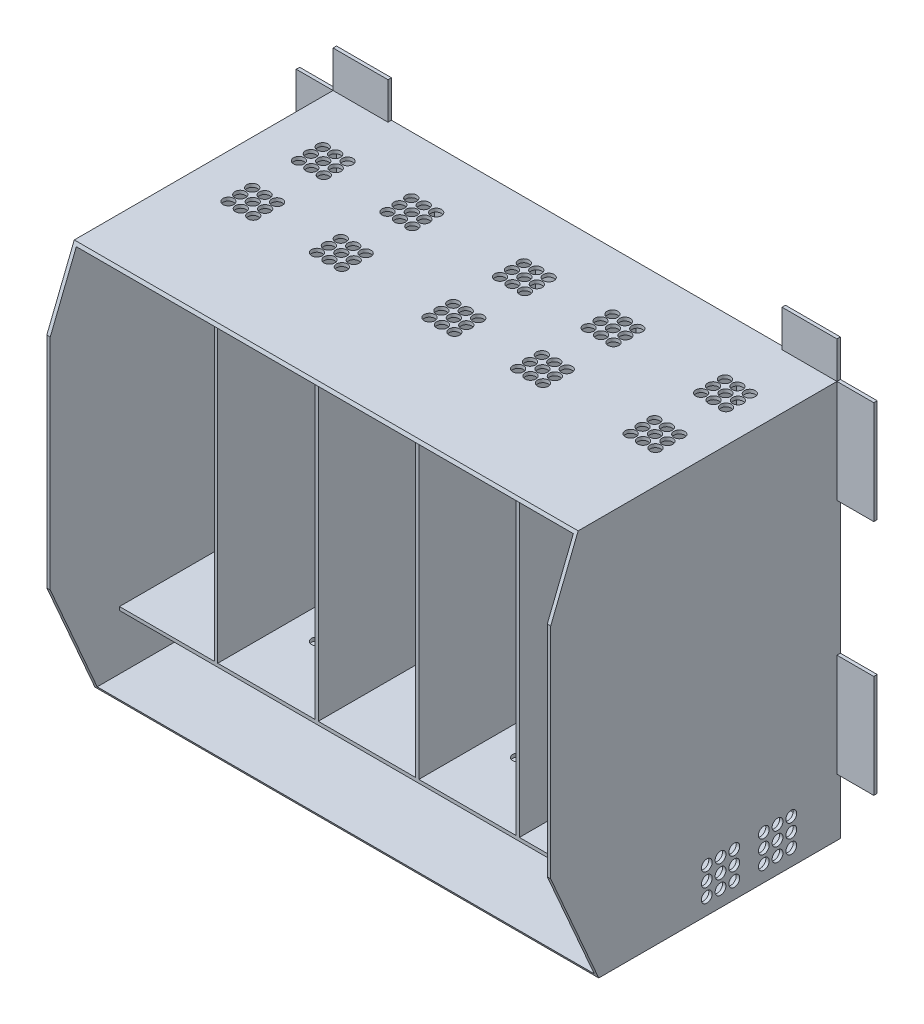
SolidWorks part; units mm, degrees
material "6061-T6 (SS)"
ref_plane "X-Y Datum" through (0, 0, 0) normal (0, 0, 1) x (1, 0, 0)
ref_plane "X-Z Datum" through (0, 0, 0) normal (0, 1, 0) x (1, 0, 0)
ref_plane "Y-Z Datum" through (0, 0, 0) normal (1, 0, 0) x (0, 0, -1)
sketch "Sketch1" plane through (0, 0, 0) normal (0, 0, 1) x (1, 0, 0)
  line L0 (-276.2265, 0) -> (276.2265, 0) construction
  line L1 (-276.2265, 154.041) -> (276.2265, 154.041)
  line L2 (-276.2265, 154.041) -> (-276.2265, -154.041)
  line L3 (-276.2265, -154.041) -> (276.2265, -154.041)
  line L4 (276.2265, 154.041) -> (276.2265, -154.041)
  line L5 (-276.2265, 154.041) -> (276.2265, -154.041) construction
  line L6 (-276.2265, -154.041) -> (276.2265, 154.041) construction
  line L7 (-275.2105, 153.025) -> (-189.6105, 153.025) construction
  line L8 (-275.2105, 153.025) -> (-275.2105, -153.025) construction
  line L9 (-275.2105, -153.025) -> (-189.6105, -153.025) construction
  line L10 (-189.6105, 153.025) -> (-189.6105, -153.025) construction
  line L11 (-275.2105, 153.025) -> (-189.6105, -153.025) construction
  line L12 (-275.2105, -153.025) -> (-189.6105, 153.025) construction
  line L13 (-188.5945, -154.041) -> (-188.5945, 154.041)
  line L14 (-279.4015, 157.216) -> (279.4015, 157.216)
  line L15 (279.4015, 157.216) -> (279.4015, -157.216)
  line L16 (-279.4015, -157.216) -> (279.4015, -157.216)
  line L17 (-279.4015, 157.216) -> (-279.4015, -157.216)
  line L18 (-185.4195, -154.041) -> (-185.4195, 154.041)
  line L19 (-188.5945, 0) -> (-185.4195, 0) construction
  line L20 (-182.2465, 153.025) -> (-182.2465, -153.025) construction
  line L21 (-182.2465, 153.025) -> (-96.6465, 153.025) construction
  line L22 (-96.6465, 153.025) -> (-96.6465, -153.025) construction
  line L23 (-182.2465, -153.025) -> (-96.6465, -153.025) construction
  line L24 (-95.6305, -154.041) -> (-95.6305, 154.041)
  line L25 (-92.4555, -154.041) -> (-92.4555, 154.041)
  line L26 (-89.2825, 153.025) -> (-89.2825, -153.025) construction
  line L27 (-89.2825, 153.025) -> (-3.6825, 153.025) construction
  line L28 (-3.6825, 153.025) -> (-3.6825, -153.025) construction
  line L29 (-89.2825, -153.025) -> (-3.6825, -153.025) construction
  line L30 (-2.6665, -154.041) -> (-2.6665, 154.041)
  line L31 (0.5085, -154.041) -> (0.5085, 154.041)
  line L32 (3.6815, 153.025) -> (3.6815, -153.025) construction
  line L33 (3.6815, 153.025) -> (89.2815, 153.025) construction
  line L34 (89.2815, 153.025) -> (89.2815, -153.025) construction
  line L35 (3.6815, -153.025) -> (89.2815, -153.025) construction
  line L36 (90.2975, -154.041) -> (90.2975, 154.041)
  line L37 (93.4725, -154.041) -> (93.4725, 154.041)
  line L38 (96.6455, 153.025) -> (96.6455, -153.025) construction
  line L39 (96.6455, 153.025) -> (182.2455, 153.025) construction
  line L40 (182.2455, 153.025) -> (182.2455, -153.025) construction
  line L41 (96.6455, -153.025) -> (182.2455, -153.025) construction
  line L42 (183.2615, -154.041) -> (183.2615, 154.041)
  line L43 (186.4365, -154.041) -> (186.4365, 154.041)
  line L44 (-182.2465, -153.025) -> (-96.6465, 153.025) construction
  line L45 (-182.2465, 153.025) -> (-96.6465, -153.025) construction
  line L46 (-89.2825, -153.025) -> (-3.6825, 153.025) construction
  line L47 (-89.2825, 153.025) -> (-3.6825, -153.025) construction
  line L48 (3.6815, -153.025) -> (89.2815, 153.025) construction
  line L49 (3.6815, 153.025) -> (89.2815, -153.025) construction
  line L50 (96.6455, -153.025) -> (182.2455, 153.025) construction
  line L51 (96.6455, 153.025) -> (182.2455, -153.025) construction
  line L52 (-276.2265, -157.216) -> (-276.2265, -208.016)
  line L53 (-279.4015, -157.216) -> (279.4015, -157.216)
  line L54 (-279.4015, -157.216) -> (-279.4015, -210.302)
  line L56 (279.4015, -157.216) -> (279.4015, -397.1906)
  line L58 (276.2265, -157.216) -> (276.2265, -392.7808)
  line L59 (186.4365, -154.041) -> (186.4365, -210.302)
  line L60 (183.2615, -157.216) -> (183.2615, -208.016)
  line L61 (186.4365, 154.041) -> (186.4365, 157.216)
  line L62 (-276.2265, -208.016) -> (276.2265, -392.7808) construction
  line L63 (-276.2265, -208.016) -> (183.2615, -208.016)
  line L64 (-279.4015, -210.302) -> (186.4365, -210.302)
  line L65 (-279.4015, -210.302) -> (279.4015, -397.1906) construction
  point P0 (0, 0)
  point P6 (-232.4105, 0)
  point P23 (-187.007, 0)
  point P24 (-139.4465, 0)
  dimension "D1" = 306.05
  dimension "D2" = 85.6
  dimension "D3" = 1.016
  dimension "D4" = 1.016
  dimension "D5" = 1.016
  dimension "D8" = 45.4035
  dimension "D10" = 89.789
  dimension "D12" = 92.964
  dimension "D13" = 89.79
  dimension "D14" = 50.8
  dimension "D16" = 2.286
  dimension "D6" = 3.175
  dimension "D7" = 3.175
  dimension "D15" = 3.175
  dimension "D9" = 5
  dimension "D11" = 5
extrude "Boss-Extrude1" add sketch "Sketch1" along normal blind 3.175 contours L3 L43 L1 L42 | L54 L64 L59 L53 L60 L63 L52 L16 | L52 L63 L60 L16 | L3 L42 L1 L37 | L3 L36 L1 L31 | L3 L31 L1 L30 | L3 L37 L1 L36 | L3 L30 L1 L25 | L1 L61 L14 L17 L16 L53 L59 L3 L2 | L3 L24 L1 L18 | L3 L13 L1 L2 | L3 L18 L1 L13 | L3 L25 L1 L24 region at (-276.7885, 0, 0) region at (-232.4105, 0, 0) region at (-187.007, 0, 0) region at (-140.525, 0, 0) region at (-94.043, 0, 0) region at (-47.561, 0, 0) region at (-1.079, 0, 0) region at (45.403, 0, 0) region at (91.885, 0, 0) region at (138.367, 0, 0) region at (184.849, 0, 0) region at (185.9676, -183.759, 0) region at (-46.4825, -182.616, 0)
sketch "Sketch2" plane through (0, 0, 3.175) normal (0, 0, 1) x (1, 0, 0)
  line L0 (-188.5945, -154.041) -> (-188.5945, 154.041) construction
  line L1 (-95.6305, -154.041) -> (-95.6305, 154.041) construction
  line L2 (-185.4195, -154.041) -> (-185.4195, 154.041) construction
  line L3 (90.2975, -154.041) -> (90.2975, 154.041) construction
  line L4 (276.2265, 154.041) -> (-276.2265, 154.041)
  line L5 (276.2265, -154.041) -> (276.2265, 154.041)
  line L6 (-276.2265, -154.041) -> (276.2265, -154.041)
  line L7 (-276.2265, 154.041) -> (-276.2265, -154.041)
  line L8 (276.2265, 154.041) -> (-276.2265, 154.041)
  line L9 (276.2265, -154.041) -> (276.2265, 154.041)
  line L10 (-276.2265, -154.041) -> (276.2265, -154.041)
  line L11 (-276.2265, 154.041) -> (-276.2265, -154.041)
  line L12 (-279.4015, -157.216) -> (279.4015, -157.216)
  line L13 (-279.4015, -157.216) -> (279.4015, -157.216) construction
  line L14 (279.4015, 157.216) -> (279.4015, -157.216) construction
  line L15 (-279.4015, 157.216) -> (279.4015, 157.216) construction
  line L16 (-279.4015, -157.216) -> (279.4015, -157.216)
  line L20 (0.5085, -154.041) -> (0.5085, 154.041) construction
  line L21 (-2.6665, -154.041) -> (-2.6665, 154.041) construction
  line L22 (-92.4555, -154.041) -> (-92.4555, 154.041) construction
  line L23 (186.4365, -154.041) -> (186.4365, 154.041) construction
  line L24 (183.2615, -154.041) -> (183.2615, 154.041) construction
  line L25 (93.4725, -154.041) -> (93.4725, 154.041) construction
  line L26 (-188.5945, -154.041) -> (-188.5945, 154.041)
  line L27 (-95.6305, -154.041) -> (-95.6305, 154.041)
  line L28 (-185.4195, -154.041) -> (-185.4195, 154.041)
  line L29 (90.2975, -154.041) -> (90.2975, 154.041)
  line L30 (0.5085, -154.041) -> (0.5085, 154.041)
  line L31 (-2.6665, -154.041) -> (-2.6665, 154.041)
  line L32 (-92.4555, -154.041) -> (-92.4555, 154.041)
  line L33 (186.4365, -154.041) -> (186.4365, 154.041)
  line L34 (183.2615, -154.041) -> (183.2615, 154.041)
  line L35 (93.4725, -154.041) -> (93.4725, 154.041)
  line L36 (-279.4015, 157.216) -> (-279.4015, -157.216) construction
  line L37 (-279.4015, -157.216) -> (279.4015, -157.216) construction
  line L38 (-279.4015, -157.216) -> (-279.4015, -210.302) construction
  line L41 (-276.2265, -157.216) -> (-276.2265, -208.016) construction
  line L44 (-276.2265, 154.041) -> (276.2265, 154.041) construction
  line L45 (276.2265, 154.041) -> (276.2265, -154.041) construction
  line L46 (-276.2265, -154.041) -> (276.2265, -154.041) construction
  line L47 (-276.2265, 154.041) -> (-276.2265, -154.041) construction
  line L48 (-188.5945, -154.041) -> (-188.5945, 154.041)
  line L49 (-95.6305, -154.041) -> (-95.6305, 154.041)
  line L50 (-185.4195, -154.041) -> (-185.4195, 154.041)
  line L51 (-279.4015, -157.216) -> (279.4015, -157.216)
  line L52 (279.4015, 157.216) -> (279.4015, -157.216)
  line L53 (-279.4015, 157.216) -> (279.4015, 157.216)
  line L54 (-279.4015, 157.216) -> (-279.4015, -157.216)
  line L55 (-279.4015, -157.216) -> (279.4015, -157.216)
  line L56 (-279.4015, -157.216) -> (-279.4015, -210.302)
  line L59 (90.2975, -154.041) -> (90.2975, 154.041)
  line L60 (0.5085, -154.041) -> (0.5085, 154.041)
  line L61 (-2.6665, -154.041) -> (-2.6665, 154.041)
  line L62 (-92.4555, -154.041) -> (-92.4555, 154.041)
  line L63 (186.4365, -154.041) -> (186.4365, 154.041)
  line L64 (183.2615, -154.041) -> (183.2615, 154.041)
  line L65 (93.4725, -154.041) -> (93.4725, 154.041)
  line L66 (-276.2265, -157.216) -> (-276.2265, -208.016)
  line L67 (-279.4015, -210.302) -> (186.4365, -210.302) construction
  line L69 (-276.2265, 154.041) -> (276.2265, 154.041)
  line L70 (276.2265, 154.041) -> (276.2265, -154.041)
  line L71 (-276.2265, -154.041) -> (276.2265, -154.041)
  line L72 (-276.2265, 154.041) -> (-276.2265, -154.041)
  line L73 (183.2615, -157.216) -> (183.2615, -208.016) construction
  line L74 (186.4365, 154.041) -> (186.4365, 157.216) construction
  line L75 (186.4365, -154.041) -> (186.4365, -210.302) construction
  line L76 (-188.5945, -154.041) -> (-188.5945, 154.041)
  line L77 (-95.6305, -154.041) -> (-95.6305, 154.041)
  line L78 (-185.4195, -154.041) -> (-185.4195, 154.041)
  line L79 (-279.4015, -157.216) -> (279.4015, -157.216)
  line L80 (279.4015, 157.216) -> (279.4015, -157.216)
  line L81 (-279.4015, 157.216) -> (279.4015, 157.216)
  line L82 (-279.4015, 157.216) -> (-279.4015, -157.216)
  line L83 (-279.4015, -157.216) -> (279.4015, -157.216)
  line L84 (-279.4015, -157.216) -> (-279.4015, -210.302)
  line L85 (-276.2265, -208.016) -> (183.2615, -208.016) construction
  line L87 (90.2975, -154.041) -> (90.2975, 154.041)
  line L88 (0.5085, -154.041) -> (0.5085, 154.041)
  line L89 (-2.6665, -154.041) -> (-2.6665, 154.041)
  line L90 (-92.4555, -154.041) -> (-92.4555, 154.041)
  line L91 (183.2615, -154.041) -> (183.2615, 154.041)
  line L92 (93.4725, -154.041) -> (93.4725, 154.041)
  line L93 (183.2615, -157.216) -> (183.2615, -208.016)
  line L94 (-276.2265, -157.216) -> (-276.2265, -208.016)
  line L97 (186.4365, 154.041) -> (186.4365, 157.216)
  line L98 (186.4365, -154.041) -> (186.4365, 154.041)
  line L99 (186.4365, -154.041) -> (186.4365, -210.302)
  line L100 (-276.2265, 154.041) -> (276.2265, 154.041)
  line L101 (276.2265, 154.041) -> (276.2265, -154.041)
  line L102 (-276.2265, -154.041) -> (276.2265, -154.041)
  line L103 (-276.2265, 154.041) -> (-276.2265, -154.041)
  line L104 (-188.5945, -154.041) -> (-188.5945, 154.041)
  line L106 (-95.6305, -154.041) -> (-95.6305, 154.041)
  line L107 (-185.4195, -154.041) -> (-185.4195, 154.041)
  line L108 (-279.4015, -157.216) -> (279.4015, -157.216)
  line L109 (279.4015, 157.216) -> (279.4015, -157.216)
  line L110 (-279.4015, 157.216) -> (279.4015, 157.216)
  line L111 (-279.4015, 157.216) -> (-279.4015, -157.216)
  line L112 (-279.4015, -157.216) -> (279.4015, -157.216)
  line L113 (186.4365, 154.041) -> (186.4365, 157.216)
  line L114 (186.4365, -154.041) -> (186.4365, 154.041)
  line L115 (186.4365, -154.041) -> (186.4365, -210.302)
  line L116 (-279.4015, -210.302) -> (186.4365, -210.302)
  line L117 (-279.4015, -157.216) -> (-279.4015, -210.302)
  line L118 (90.2975, -154.041) -> (90.2975, 154.041)
  line L119 (0.5085, -154.041) -> (0.5085, 154.041)
  line L120 (-2.6665, -154.041) -> (-2.6665, 154.041)
  line L121 (-92.4555, -154.041) -> (-92.4555, 154.041)
  line L122 (183.2615, -154.041) -> (183.2615, 154.041)
  line L123 (93.4725, -154.041) -> (93.4725, 154.041)
  line L124 (183.2615, -157.216) -> (183.2615, -208.016)
  line L125 (-276.2265, -208.016) -> (183.2615, -208.016)
  line L126 (-276.2265, -157.216) -> (-276.2265, -208.016)
  line L128 (-276.2265, 154.041) -> (276.2265, 154.041)
  line L129 (276.2265, 154.041) -> (276.2265, -154.041)
  line L130 (-276.2265, -154.041) -> (276.2265, -154.041)
  line L131 (-276.2265, 154.041) -> (-276.2265, -154.041)
  line M9 (186.4365, 157.216) -> (-279.4015, 157.216)
  line M10 (-279.4015, 157.216) -> (-279.4015, -210.302)
  line M86 (186.4365, -210.302) -> (186.4365, 157.216)
  line M120 (-279.4015, -210.302) -> (186.4365, -210.302)
  dimension "D1" = 0
  dimension "D2" = 0
extrude "Boss-Extrude2" add sketch "Sketch2" along normal blind 200.6 contours L125 L66 L16 L83 L93 M10 M120 M86 | L16 L55 L83 L10 L11 L8 M10 M86 M9 | L34 L10 L8 M86 | L10 L35 L8 L29 | L10 L28 L8 L26 | L10 L32 L8 L27 | L31 L10 L30 L8 region at (184.849, 0, 3.175) region at (184.849, 154.603, 3.175) region at (91.885, 0, 3.175) region at (185.9676, -183.759, 3.175) region at (-1.079, 0, 3.175) region at (-94.043, 0, 3.175) region at (-187.007, 0, 3.175)
sketch "Sketch11" plane through (0, 0, 203.775) normal (0, 0, 1) x (1, 0, 0)
  line L0 (-188.5945, -154.041) -> (-188.5945, 154.041) construction
  line L2 (-95.6305, -154.041) -> (-95.6305, 154.041) construction
  line L3 (-185.4195, -154.041) -> (-185.4195, 154.041) construction
  line L4 (186.4365, -210.302) -> (186.4365, 157.216)
  line L5 (186.4365, 157.216) -> (-279.4015, 157.216)
  line L6 (-279.4015, 157.216) -> (-279.4015, -210.302)
  line L7 (-279.4015, -210.302) -> (186.4365, -210.302)
  line L8 (186.4365, -210.302) -> (186.4365, 157.216)
  line L9 (186.4365, 157.216) -> (-279.4015, 157.216)
  line L10 (-279.4015, 157.216) -> (-279.4015, -210.302)
  line L11 (-279.4015, -210.302) -> (186.4365, -210.302)
  line L12 (-279.4015, -157.216) -> (279.4015, -157.216) construction
  line L14 (-279.4015, 157.216) -> (279.4015, 157.216) construction
  line L15 (-279.4015, 157.216) -> (-279.4015, -157.216) construction
  line L16 (-279.4015, -157.216) -> (279.4015, -157.216) construction
  line L17 (186.4365, 154.041) -> (186.4365, 157.216) construction
  line L18 (186.4365, -154.041) -> (186.4365, 154.041) construction
  line L19 (186.4365, -154.041) -> (186.4365, -210.302) construction
  line L20 (-279.4015, -210.302) -> (186.4365, -210.302) construction
  line L21 (-279.4015, -157.216) -> (-279.4015, -210.302) construction
  line L22 (90.2975, -154.041) -> (90.2975, 154.041) construction
  line L23 (0.5085, -154.041) -> (0.5085, 154.041) construction
  line L24 (-2.6665, -154.041) -> (-2.6665, 154.041) construction
  line L25 (-92.4555, -154.041) -> (-92.4555, 154.041) construction
  line L26 (183.2615, -154.041) -> (183.2615, 154.041) construction
  line L27 (93.4725, -154.041) -> (93.4725, 154.041) construction
  line L28 (183.2615, -157.216) -> (183.2615, -208.016) construction
  line L29 (-276.2265, -208.016) -> (183.2615, -208.016) construction
  line L30 (-276.2265, -157.216) -> (-276.2265, -208.016) construction
  line L32 (-276.2265, 154.041) -> (276.2265, 154.041) construction
  line L34 (-276.2265, -154.041) -> (276.2265, -154.041) construction
  line L35 (-276.2265, 154.041) -> (-276.2265, -154.041) construction
  line L36 (-188.5945, -154.041) -> (-188.5945, 154.041)
  line L37 (183.2615, -157.216) -> (183.2615, -154.041)
  line L38 (-95.6305, -154.041) -> (-95.6305, 154.041)
  line L39 (-185.4195, -154.041) -> (-185.4195, 154.041)
  line L40 (-279.4015, -157.216) -> (186.4365, -157.216)
  line L42 (-279.4015, 157.216) -> (186.4365, 157.216)
  line L43 (-279.4015, 157.216) -> (-279.4015, -157.216)
  line L44 (-279.4015, -157.216) -> (186.4365, -157.216)
  line L45 (186.4365, 154.041) -> (186.4365, 157.216)
  line L46 (186.4365, -154.041) -> (186.4365, 154.041)
  line L47 (186.4365, -154.041) -> (186.4365, -210.302)
  line L48 (-279.4015, -210.302) -> (186.4365, -210.302)
  line L49 (-279.4015, -157.216) -> (-279.4015, -210.302)
  line L50 (90.2975, -154.041) -> (90.2975, 154.041)
  line L51 (0.5085, -154.041) -> (0.5085, 154.041)
  line L52 (-2.6665, -154.041) -> (-2.6665, 154.041)
  line L53 (-92.4555, -154.041) -> (-92.4555, 154.041)
  line L54 (183.2615, -154.041) -> (183.2615, 154.041)
  line L55 (93.4725, -154.041) -> (93.4725, 154.041)
  line L56 (183.2615, -157.216) -> (183.2615, -208.016)
  line L57 (-276.2265, -208.016) -> (183.2615, -208.016)
  line L58 (-276.2265, -157.216) -> (-276.2265, -208.016)
  line L59 (-276.2265, -157.216) -> (-276.2265, -154.041)
  line L60 (-276.2265, 154.041) -> (186.4365, 154.041)
  line L62 (-276.2265, -154.041) -> (186.4365, -154.041)
  line L63 (-276.2265, 154.041) -> (-276.2265, -154.041)
  line M7 (-185.4195, 154.041) -> (-95.6305, 154.041)
  line M11 (-92.4555, 154.041) -> (-2.6665, 154.041)
  line M15 (0.5085, 154.041) -> (90.2975, 154.041)
  line M19 (93.4725, 154.041) -> (183.2615, 154.041)
  line M20 (183.2615, 154.041) -> (183.2615, -154.041)
  line M21 (186.4365, -210.302) -> (186.4365, 157.216)
  line M22 (186.4365, 157.216) -> (-279.4015, 157.216)
  line M23 (-279.4015, 157.216) -> (-279.4015, -210.302)
  line M24 (-279.4015, -210.302) -> (186.4365, -210.302)
  line M25 (-276.2265, -208.016) -> (-276.2265, -157.216)
  line M27 (183.2615, -157.216) -> (183.2615, -208.016)
  line M28 (183.2615, -208.016) -> (-276.2265, -208.016)
  line M31 (-276.2265, -154.041) -> (-276.2265, 154.041)
  line M32 (-276.2265, 154.041) -> (-188.5945, 154.041)
  dimension "D1" = 0
extrude "Boss-Extrude8" add sketch "Sketch11" along normal blind 64.05 contours L40 L10 M24 M21 M27 M28 M25 | L62 L60 M20 M21 | L62 L37 L40 L8 | L60 L40 L59 M32 M7 M11 M15 M19 M21 M22 M23 M31 region at (-46.4825, -209.8331, 203.775) region at (184.849, -155.6285, 203.775) region at (184.849, 0, 203.775) region at (-278.8395, 0, 203.775)
sketch "Sketch10" plane through (0, 0, 0) normal (0, 0, 1) x (1, 0, 0)
  line L1 (186.4365, 157.216) -> (220.4725, 157.216)
  line L2 (186.4365, 157.216) -> (186.4365, 61.966)
  line L3 (186.4365, 61.966) -> (220.4725, 61.966)
  line L4 (186.4365, -210.302) -> (186.4365, 157.216)
  line L5 (-279.4015, -210.302) -> (186.4365, -210.302)
  line L6 (-279.4015, 157.216) -> (-279.4015, -210.302)
  line L7 (186.4365, 157.216) -> (-279.4015, 157.216)
  line L8 (186.4365, -210.302) -> (186.4365, 157.216)
  line L10 (-279.4015, 157.216) -> (-279.4015, -210.302)
  line L11 (186.4365, 157.216) -> (-279.4015, 157.216)
  line L12 (220.4725, 157.216) -> (220.4725, 61.966)
  line L13 (-276.2265, -157.216) -> (183.2615, -157.216) construction
  line L14 (-276.2265, -157.216) -> (183.2615, -157.216)
  line L15 (186.4365, -157.216) -> (220.4725, -157.216)
  line L16 (186.4365, -157.216) -> (186.4365, -61.966)
  line L17 (186.4365, -61.966) -> (220.4725, -61.966)
  line L18 (220.4725, -157.216) -> (220.4725, -61.966)
  line L19 (186.4365, 157.216) -> (135.6365, 157.216)
  line L20 (186.4365, 157.216) -> (186.4365, 191.252)
  line L21 (186.4365, 191.252) -> (135.6365, 191.252)
  line L22 (135.6365, 157.216) -> (135.6365, 191.252)
  line L26 (-279.4015, -210.302) -> (186.4365, -210.302)
  dimension "D2" = 34.036
  dimension "D3" = 95.25
  dimension "D4" = 50.8
  dimension "D1" = 0
extrude "Boss-Extrude7" add sketch "Sketch10" along normal blind 3.175 contours L12 L1 L2 L3 | L15 L18 L17 L8 | L22 L11 L20 L21 region at (203.4545, 109.591, 0) region at (161.0365, 174.234, 0) region at (203.4545, -109.591, 0)
ref_plane "Plane1" through (-46.4825, 0, 0) normal (-1, 0, 0) x (0, 0, 1)
mirror "Mirror1" about plane through (-46.4825, 0, 0) normal (-1, 0, 0) of "Boss-Extrude7"
sketch "Sketch12" plane through (186.4365, 0, 0) normal (1, 0, 0) x (0, 0, -1)
  line L0 (-223.375, -210.302) -> (-267.825, -108.702)
  line L1 (-267.825, 93.716) -> (-242.425, 157.216)
  line L10 (0, -210.302) -> (0, -157.216)
  line L11 (0, -157.216) -> (-3.175, -157.216)
  line L12 (-3.175, -157.216) -> (-3.175, -61.966)
  line L13 (-3.175, -61.966) -> (0, -61.966)
  line L14 (0, -61.966) -> (0, 61.966)
  line L15 (0, 61.966) -> (-3.175, 61.966)
  line L16 (-3.175, 61.966) -> (-3.175, 157.216)
  line L17 (-3.175, 157.216) -> (-267.825, 157.216)
  line L18 (-267.825, 157.216) -> (-267.825, -210.302)
  line L19 (-267.825, -210.302) -> (0, -210.302)
  line L20 (0, -210.302) -> (0, -157.216)
  line L21 (0, -157.216) -> (-3.175, -157.216)
  line L22 (-3.175, -157.216) -> (-3.175, -61.966)
  line L23 (-3.175, -61.966) -> (0, -61.966)
  line L24 (0, -61.966) -> (0, 61.966)
  line L25 (0, 61.966) -> (-3.175, 61.966)
  line L26 (-3.175, 61.966) -> (-3.175, 157.216)
  line L27 (-3.175, 157.216) -> (-267.825, 157.216)
  line L28 (-267.825, 157.216) -> (-267.825, -210.302)
  line L29 (-267.825, -210.302) -> (0, -210.302)
  line M18 (-3.175, 157.216) -> (-267.825, 157.216)
  line M19 (-267.825, 157.216) -> (-267.825, -210.302)
  line M20 (-267.825, -210.302) -> (0, -210.302)
  dimension "D2" = 44.45
  dimension "D3" = 101.6
  dimension "D4" = 25.4
  dimension "D5" = 63.5
  dimension "D1" = 0
extrude "Cut-Extrude1" cut sketch "Sketch12" against normal through all contours L0 M20 M19 | L1 M19 M18 region at (186.4365, -176.4353, 253.0083) region at (186.4365, 136.0493, 259.3583)
sketch "Sketch13" plane through (0, 157.216, 0) normal (0, 1, 0) x (1, 0, 0)
  circle A0 centre (-238.9105, -118.4317) radius 5 construction
  circle A1 centre (-238.9105, -129.4317) radius 5 construction
  circle A2 centre (-238.9105, -140.4317) radius 5 construction
  circle A3 centre (-227.4105, -140.4317) radius 5 construction
  circle A4 centre (-227.4105, -129.4317) radius 5 construction
  circle A5 centre (-227.4105, -118.4317) radius 5 construction
  circle A6 centre (-215.9105, -118.4317) radius 5 construction
  circle A7 centre (-215.9105, -129.4317) radius 5 construction
  circle A8 centre (-215.9105, -140.4317) radius 5 construction
  circle A9 centre (-238.9105, -118.4317) radius 5
  circle A10 centre (-238.9105, -129.4317) radius 5
  circle A11 centre (-238.9105, -140.4317) radius 5
  circle A12 centre (-227.4105, -140.4317) radius 5
  circle A13 centre (-227.4105, -129.4317) radius 5
  circle A14 centre (-227.4105, -118.4317) radius 5
  circle A15 centre (-215.9105, -118.4317) radius 5
  circle A16 centre (-215.9105, -129.4317) radius 5
  circle A17 centre (-215.9105, -140.4317) radius 5
  circle A18 centre (-215.9105, -53.2317) radius 5 construction
  circle A19 centre (-215.9105, -53.2317) radius 5
  circle A20 centre (-215.9105, -75.2317) radius 5 construction
  circle A21 centre (-227.4105, -75.2317) radius 5 construction
  circle A22 centre (-238.9105, -75.2317) radius 5 construction
  circle A23 centre (-238.9105, -64.2317) radius 5 construction
  circle A24 centre (-227.4105, -64.2317) radius 5 construction
  circle A25 centre (-215.9105, -64.2317) radius 5 construction
  circle A26 centre (-227.4105, -53.2317) radius 5 construction
  circle A27 centre (-238.9105, -53.2317) radius 5 construction
  circle A28 centre (-215.9105, -75.2317) radius 5
  circle A29 centre (-227.4105, -75.2317) radius 5
  circle A30 centre (-238.9105, -75.2317) radius 5
  circle A31 centre (-238.9105, -64.2317) radius 5
  circle A32 centre (-227.4105, -64.2317) radius 5
  circle A33 centre (-215.9105, -64.2317) radius 5
  circle A34 centre (-215.9105, -53.2317) radius 5
  circle A35 centre (-227.4105, -53.2317) radius 5
  circle A36 centre (-238.9105, -53.2317) radius 5
  circle A37 centre (-145.525, -140.4317) radius 5 construction
  circle A38 centre (-145.525, -129.4317) radius 5 construction
  circle A39 centre (-145.525, -118.4317) radius 5 construction
  circle A40 centre (-157.025, -118.4317) radius 5 construction
  circle A41 centre (-157.025, -129.4317) radius 5 construction
  circle A42 centre (-157.025, -140.4317) radius 5 construction
  circle A43 centre (-145.525, -140.4317) radius 5
  circle A44 centre (-145.525, -129.4317) radius 5
  circle A45 centre (-145.525, -118.4317) radius 5
  circle A46 centre (-157.025, -118.4317) radius 5
  circle A47 centre (-157.025, -129.4317) radius 5
  circle A48 centre (-157.025, -140.4317) radius 5
  circle A49 centre (-134.025, -118.4317) radius 5 construction
  circle A50 centre (-134.025, -140.4317) radius 5 construction
  circle A51 centre (-134.025, -129.4317) radius 5 construction
  circle A52 centre (-134.025, -118.4317) radius 5
  circle A53 centre (-134.025, -140.4317) radius 5
  circle A54 centre (-134.025, -129.4317) radius 5
  circle A55 centre (-157.025, -75.2317) radius 5 construction
  circle A56 centre (-145.525, -75.2317) radius 5 construction
  circle A57 centre (-134.025, -75.2317) radius 5 construction
  circle A58 centre (-157.025, -75.2317) radius 5
  circle A59 centre (-145.525, -75.2317) radius 5
  circle A60 centre (-134.025, -75.2317) radius 5
  circle A61 centre (-134.025, -53.2317) radius 5 construction
  circle A62 centre (-145.525, -53.2317) radius 5 construction
  circle A63 centre (-157.025, -53.2317) radius 5 construction
  circle A64 centre (-157.025, -64.2317) radius 5 construction
  circle A65 centre (-134.025, -64.2317) radius 5 construction
  circle A66 centre (-145.525, -64.2317) radius 5 construction
  circle A67 centre (-134.025, -53.2317) radius 5
  circle A68 centre (-145.525, -53.2317) radius 5
  circle A69 centre (-157.025, -53.2317) radius 5
  circle A70 centre (-157.025, -64.2317) radius 5
  circle A71 centre (-134.025, -64.2317) radius 5
  circle A72 centre (-145.525, -64.2317) radius 5
  point P109 (0, 0)
  point P110 (0, 0)
extrude "Cut-Extrude2" cut sketch "Sketch13" against normal up to surface (3.175 mm away) contours A35 | A36 | A31 | A32 | A33 | A30 | A29 | A28 | A10 | A13 | A11 | A12 | A17 | A16 | A15 | A19 | A9 | A14 region at (-238.9105, 157.216, 129.4317) region at (-238.9105, 157.216, 140.4317) region at (-227.4105, 157.216, 140.4317) region at (-227.4105, 157.216, 129.4317) region at (-215.9105, 157.216, 118.4317) region at (-215.9105, 157.216, 129.4317) region at (-215.9105, 157.216, 140.4317) region at (-215.9105, 157.216, 75.2317) region at (-227.4105, 157.216, 75.2317) region at (-238.9105, 157.216, 75.2317) region at (-238.9105, 157.216, 64.2317) region at (-227.4105, 157.216, 64.2317) region at (-215.9105, 157.216, 64.2317) region at (-227.4105, 157.216, 53.2317) region at (-238.9105, 157.216, 53.2317) up to face at (-47.3453, 154.041, 107.467)
pattern_linear "LPattern1" count 3 spacing 185.92 along (1, 0, 0) of "Cut-Extrude2"
sketch "Sketch14" plane through (0, 157.216, 0) normal (0, 1, 0) x (1, 0, 0)
  circle A1 centre (-215.9105, -53.2317) radius 5
  circle A2 centre (-215.9105, -53.2317) radius 5
  circle A3 centre (-215.9105, -140.4317) radius 5
  circle A4 centre (-215.9105, -140.4317) radius 5
  circle A5 centre (-215.9105, -129.4317) radius 5
  circle A6 centre (-215.9105, -129.4317) radius 5
  circle A7 centre (-215.9105, -118.4317) radius 5
  circle A8 centre (-215.9105, -118.4317) radius 5
  circle A9 centre (-227.4105, -118.4317) radius 5
  circle A10 centre (-227.4105, -118.4317) radius 5
  circle A11 centre (-227.4105, -129.4317) radius 5
  circle A12 centre (-227.4105, -129.4317) radius 5
  circle A13 centre (-227.4105, -140.4317) radius 5
  circle A14 centre (-227.4105, -140.4317) radius 5
  circle A15 centre (-238.9105, -140.4317) radius 5
  circle A16 centre (-238.9105, -140.4317) radius 5
  circle A17 centre (-238.9105, -129.4317) radius 5
  circle A18 centre (-238.9105, -129.4317) radius 5
  circle A19 centre (-238.9105, -118.4317) radius 5
  circle A20 centre (-238.9105, -118.4317) radius 5
  circle A21 centre (-227.4105, -75.2317) radius 5
  circle A22 centre (-227.4105, -75.2317) radius 5
  circle A23 centre (-215.9105, -75.2317) radius 5
  circle A24 centre (-215.9105, -75.2317) radius 5
  circle A25 centre (-238.9105, -53.2317) radius 5
  circle A26 centre (-238.9105, -53.2317) radius 5
  circle A27 centre (-227.4105, -53.2317) radius 5
  circle A28 centre (-227.4105, -53.2317) radius 5
  circle A29 centre (-215.9105, -53.2317) radius 5
  circle A30 centre (-215.9105, -53.2317) radius 5
  circle A31 centre (-215.9105, -64.2317) radius 5
  circle A32 centre (-215.9105, -64.2317) radius 5
  circle A33 centre (-227.4105, -64.2317) radius 5
  circle A34 centre (-227.4105, -64.2317) radius 5
  circle A35 centre (-238.9105, -64.2317) radius 5
  circle A36 centre (-238.9105, -64.2317) radius 5
  circle A37 centre (-238.9105, -75.2317) radius 5
  circle A38 centre (-238.9105, -75.2317) radius 5
  circle A39 centre (-134.025, -118.4317) radius 5
  circle A40 centre (-134.025, -118.4317) radius 5
  circle A41 centre (-157.025, -140.4317) radius 5
  circle A42 centre (-157.025, -140.4317) radius 5
  circle A43 centre (-157.025, -129.4317) radius 5
  circle A44 centre (-157.025, -129.4317) radius 5
  circle A45 centre (-157.025, -118.4317) radius 5
  circle A46 centre (-157.025, -118.4317) radius 5
  circle A47 centre (-145.525, -118.4317) radius 5
  circle A48 centre (-145.525, -118.4317) radius 5
  circle A49 centre (-145.525, -129.4317) radius 5
  circle A50 centre (-145.525, -129.4317) radius 5
  circle A51 centre (-145.525, -140.4317) radius 5
  circle A52 centre (-145.525, -140.4317) radius 5
  circle A53 centre (-134.025, -75.2317) radius 5
  circle A54 centre (-134.025, -75.2317) radius 5
  circle A55 centre (-145.525, -75.2317) radius 5
  circle A56 centre (-145.525, -75.2317) radius 5
  circle A57 centre (-157.025, -75.2317) radius 5
  circle A58 centre (-157.025, -75.2317) radius 5
  circle A59 centre (-134.025, -129.4317) radius 5
  circle A60 centre (-134.025, -129.4317) radius 5
  circle A61 centre (-134.025, -140.4317) radius 5
  circle A62 centre (-134.025, -140.4317) radius 5
  circle A63 centre (-145.525, -64.2317) radius 5
  circle A64 centre (-145.525, -64.2317) radius 5
  circle A65 centre (-134.025, -64.2317) radius 5
  circle A66 centre (-134.025, -64.2317) radius 5
  circle A67 centre (-157.025, -64.2317) radius 5
  circle A68 centre (-157.025, -64.2317) radius 5
  circle A69 centre (-157.025, -53.2317) radius 5
  circle A70 centre (-157.025, -53.2317) radius 5
  circle A71 centre (-145.525, -53.2317) radius 5
  circle A72 centre (-145.525, -53.2317) radius 5
  circle A73 centre (-134.025, -53.2317) radius 5
  circle A74 centre (-134.025, -53.2317) radius 5
  dimension "D1" = 0
  dimension "D2" = 0
  dimension "D3" = 0
  dimension "D4" = 0
  dimension "D5" = 0
  dimension "D6" = 0
  dimension "D7" = 0
  dimension "D8" = 0
  dimension "D9" = 0
  dimension "D10" = 0
  dimension "D11" = 0
  dimension "D12" = 0
  dimension "D13" = 0
  dimension "D14" = 0
  dimension "D15" = 0
  dimension "D16" = 0
  dimension "D17" = 0
  dimension "D18" = 0
  dimension "D19" = 0
  dimension "D20" = 0
  dimension "D21" = 0
  dimension "D22" = 0
  dimension "D23" = 0
  dimension "D24" = 0
  dimension "D25" = 0
  dimension "D26" = 0
  dimension "D27" = 0
  dimension "D28" = 0
  dimension "D29" = 0
  dimension "D30" = 0
  dimension "D31" = 0
  dimension "D32" = 0
  dimension "D33" = 0
  dimension "D34" = 0
  dimension "D35" = 0
  dimension "D36" = 0
  dimension "D37" = 0
extrude "Cut-Extrude3" cut sketch "Sketch14" against normal up to surface (3.175 mm away) contours A42 | A52 | A62 | A60 | A50 | A44 | A46 | A48 | A40 | A56 | A54 | A66 | A64 | A68 | A70 | A72 | A74 | A58 region at (-134.025, 157.216, 118.4317) region at (-157.025, 157.216, 140.4317) region at (-157.025, 157.216, 129.4317) region at (-157.025, 157.216, 118.4317) region at (-145.525, 157.216, 118.4317) region at (-145.525, 157.216, 129.4317) region at (-145.525, 157.216, 140.4317) region at (-134.025, 157.216, 75.2317) region at (-145.525, 157.216, 75.2317) region at (-134.025, 157.216, 129.4317) region at (-134.025, 157.216, 140.4317) region at (-145.525, 157.216, 64.2317) region at (-134.025, 157.216, 64.2317) region at (-157.025, 157.216, 64.2317) region at (-157.025, 157.216, 53.2317) region at (-145.525, 157.216, 53.2317) region at (-134.025, 157.216, 53.2317) up to face at (-36.4905, 154.041, 140.4317)
pattern_linear "LPattern2" count 2 spacing 185.92 along (1, 0, 0) of "Cut-Extrude3"
sketch "Sketch16" plane through (0, -157.216, 0) normal (0, -1, 0) x (1, 0, 0)
  circle A0 centre (-215.9105, 140.4317) radius 5 construction
  circle A1 centre (-227.4105, 140.4317) radius 5 construction
  circle A2 centre (-238.9105, 140.4317) radius 5 construction
  circle A3 centre (-215.9105, 129.4317) radius 5 construction
  circle A4 centre (-238.9105, 129.4317) radius 5 construction
  circle A5 centre (-227.4105, 129.4317) radius 5 construction
  circle A6 centre (-215.9105, 118.4317) radius 5 construction
  circle A7 centre (-227.4105, 118.4317) radius 5 construction
  circle A8 centre (-238.9105, 118.4317) radius 5 construction
  circle A9 centre (-215.9105, 107.4317) radius 5 construction
  circle A10 centre (-227.4105, 107.4317) radius 5 construction
  circle A11 centre (-238.9105, 107.4317) radius 5 construction
  circle A12 centre (-215.9105, 96.4317) radius 5 construction
  circle A13 centre (-227.4105, 96.4317) radius 5 construction
  circle A14 centre (-238.9105, 96.4317) radius 5 construction
  circle A15 centre (-215.9105, 85.4317) radius 5 construction
  circle A16 centre (-227.4105, 74.4317) radius 5 construction
  circle A17 centre (-227.4105, 85.4317) radius 5 construction
  circle A18 centre (-238.9105, 85.4317) radius 5 construction
  circle A19 centre (-238.9105, 74.4317) radius 5 construction
  circle A20 centre (-227.4105, 63.4317) radius 5 construction
  circle A21 centre (-238.9105, 63.4317) radius 5 construction
  circle A22 centre (-238.9105, 52.4317) radius 5 construction
  circle A23 centre (-238.9105, 41.4317) radius 5 construction
  circle A24 centre (-238.9105, 30.4317) radius 5 construction
  circle A25 centre (-227.4105, 30.4317) radius 5 construction
  circle A26 centre (-215.9105, 30.4317) radius 5 construction
  circle A27 centre (-215.9105, 41.4317) radius 5 construction
  circle A28 centre (-227.4105, 41.4317) radius 5 construction
  circle A29 centre (-227.4105, 52.4317) radius 5 construction
  circle A30 centre (-215.9105, 52.4317) radius 5 construction
  circle A31 centre (-215.9105, 74.4317) radius 5 construction
  circle A32 centre (-215.9105, 63.4317) radius 5 construction
  circle A33 centre (-215.9105, 140.4317) radius 5
  circle A34 centre (-227.4105, 140.4317) radius 5
  circle A35 centre (-238.9105, 140.4317) radius 5
  circle A36 centre (-215.9105, 129.4317) radius 5
  circle A37 centre (-238.9105, 129.4317) radius 5
  circle A38 centre (-227.4105, 129.4317) radius 5
  circle A39 centre (-215.9105, 118.4317) radius 5
  circle A40 centre (-227.4105, 118.4317) radius 5
  circle A41 centre (-238.9105, 118.4317) radius 5
  circle A42 centre (-215.9105, 107.4317) radius 5
  circle A43 centre (-227.4105, 107.4317) radius 5
  circle A44 centre (-238.9105, 107.4317) radius 5
  circle A45 centre (-215.9105, 96.4317) radius 5
  circle A46 centre (-227.4105, 96.4317) radius 5
  circle A47 centre (-238.9105, 96.4317) radius 5
  circle A48 centre (-215.9105, 85.4317) radius 5
  circle A49 centre (-227.4105, 74.4317) radius 5
  circle A50 centre (-227.4105, 85.4317) radius 5
  circle A51 centre (-238.9105, 85.4317) radius 5
  circle A52 centre (-238.9105, 74.4317) radius 5
  circle A53 centre (-227.4105, 63.4317) radius 5
  circle A54 centre (-238.9105, 63.4317) radius 5
  circle A55 centre (-238.9105, 52.4317) radius 5
  circle A56 centre (-238.9105, 41.4317) radius 5
  circle A57 centre (-238.9105, 30.4317) radius 5
  circle A58 centre (-227.4105, 30.4317) radius 5
  circle A59 centre (-215.9105, 30.4317) radius 5
  circle A60 centre (-215.9105, 41.4317) radius 5
  circle A61 centre (-227.4105, 41.4317) radius 5
  circle A62 centre (-227.4105, 52.4317) radius 5
  circle A63 centre (-215.9105, 52.4317) radius 5
  circle A64 centre (-215.9105, 74.4317) radius 5
  circle A65 centre (-215.9105, 63.4317) radius 5
  circle A66 centre (-134.025, 140.4317) radius 5 construction
  circle A67 centre (-145.525, 140.4317) radius 5 construction
  circle A68 centre (-157.025, 140.4317) radius 5 construction
  circle A69 centre (-134.025, 129.4317) radius 5 construction
  circle A70 centre (-145.525, 129.4317) radius 5 construction
  circle A71 centre (-157.025, 129.4317) radius 5 construction
  circle A72 centre (-134.025, 118.4317) radius 5 construction
  circle A73 centre (-145.525, 118.4317) radius 5 construction
  circle A74 centre (-157.025, 118.4317) radius 5 construction
  circle A75 centre (-134.025, 107.4317) radius 5 construction
  circle A76 centre (-145.525, 107.4317) radius 5 construction
  circle A77 centre (-157.025, 107.4317) radius 5 construction
  circle A78 centre (-134.025, 96.4317) radius 5 construction
  circle A79 centre (-145.525, 96.4317) radius 5 construction
  circle A80 centre (-157.025, 96.4317) radius 5 construction
  circle A81 centre (-134.025, 85.4317) radius 5 construction
  circle A82 centre (-145.525, 85.4317) radius 5 construction
  circle A83 centre (-157.025, 85.4317) radius 5 construction
  circle A84 centre (-134.025, 74.4317) radius 5 construction
  circle A85 centre (-145.525, 74.4317) radius 5 construction
  circle A86 centre (-157.025, 74.4317) radius 5 construction
  circle A87 centre (-134.025, 63.4317) radius 5 construction
  circle A88 centre (-145.525, 63.4317) radius 5 construction
  circle A89 centre (-157.025, 63.4317) radius 5 construction
  circle A90 centre (-134.025, 52.4317) radius 5 construction
  circle A91 centre (-145.525, 52.4317) radius 5 construction
  circle A92 centre (-157.025, 52.4317) radius 5 construction
  circle A93 centre (-134.025, 41.4317) radius 5 construction
  circle A94 centre (-145.525, 41.4317) radius 5 construction
  circle A95 centre (-157.025, 41.4317) radius 5 construction
  circle A96 centre (-134.025, 30.4317) radius 5 construction
  circle A97 centre (-145.525, 30.4317) radius 5 construction
  circle A98 centre (-157.025, 30.4317) radius 5 construction
  circle A99 centre (-134.025, 140.4317) radius 5
  circle A100 centre (-145.525, 140.4317) radius 5
  circle A101 centre (-157.025, 140.4317) radius 5
  circle A102 centre (-134.025, 129.4317) radius 5
  circle A103 centre (-145.525, 129.4317) radius 5
  circle A104 centre (-157.025, 129.4317) radius 5
  circle A105 centre (-134.025, 118.4317) radius 5
  circle A106 centre (-145.525, 118.4317) radius 5
  circle A107 centre (-157.025, 118.4317) radius 5
  circle A108 centre (-134.025, 107.4317) radius 5
  circle A109 centre (-145.525, 107.4317) radius 5
  circle A110 centre (-157.025, 107.4317) radius 5
  circle A111 centre (-134.025, 96.4317) radius 5
  circle A112 centre (-145.525, 96.4317) radius 5
  circle A113 centre (-157.025, 96.4317) radius 5
  circle A114 centre (-134.025, 85.4317) radius 5
  circle A115 centre (-145.525, 85.4317) radius 5
  circle A116 centre (-157.025, 85.4317) radius 5
  circle A117 centre (-134.025, 74.4317) radius 5
  circle A118 centre (-145.525, 74.4317) radius 5
  circle A119 centre (-157.025, 74.4317) radius 5
  circle A120 centre (-134.025, 63.4317) radius 5
  circle A121 centre (-145.525, 63.4317) radius 5
  circle A122 centre (-157.025, 63.4317) radius 5
  circle A123 centre (-134.025, 52.4317) radius 5
  circle A124 centre (-145.525, 52.4317) radius 5
  circle A125 centre (-157.025, 52.4317) radius 5
  circle A126 centre (-134.025, 41.4317) radius 5
  circle A127 centre (-145.525, 41.4317) radius 5
  circle A128 centre (-157.025, 41.4317) radius 5
  circle A129 centre (-134.025, 30.4317) radius 5
  circle A130 centre (-145.525, 30.4317) radius 5
  circle A131 centre (-157.025, 30.4317) radius 5
extrude "Cut-Extrude5" cut sketch "Sketch16" against normal blind 3.175
pattern_linear "LPattern3" count 3 spacing 185.92 along (1, 0, 0) of "Cut-Extrude5"
sketch "Sketch17" plane through (-279.4015, 0, 0) normal (-1, 0, 0) x (0, 0, 1)
  line L0 (110.8, -169.916) -> (110.8, -195.316) construction
  line L1 (158.175, -182.616) -> (3.175, -182.616) construction
  line L2 (3.175, -157.216) -> (3.175, -208.016) construction
  line L3 (110.8, -162.616) -> (110.8, -202.616) construction
  line L4 (90.8, -162.616) -> (130.8, -162.616) construction
  line L5 (130.8, -202.616) -> (90.8, -202.616) construction
  line L6 (58.1, -162.616) -> (58.1, -202.616) construction
  line L7 (38.1, -162.616) -> (78.1, -162.616) construction
  line L8 (78.1, -202.616) -> (38.1, -202.616) construction
  line L9 (58.1, -169.916) -> (58.1, -195.316) construction
  circle A0 centre (110.8, -182.616) radius 5
  circle A1 centre (110.8, -169.916) radius 5
  circle A2 centre (110.8, -195.316) radius 5
  circle A3 centre (58.1, -182.616) radius 5
  circle A4 centre (58.1, -195.316) radius 5
  circle A5 centre (58.1, -169.916) radius 5
  point P5 (110.8, -182.616)
  point P27 (58.1, -182.616)
  dimension "D1" = 10
  dimension "D2" = 25.4
  dimension "D3" = 25.4
extrude "Cut-Extrude6" cut sketch "Sketch17" against normal through all
pattern_linear "LPattern4" count 2 spacing 12.7 along (0, 0, 1) count 2 spacing 12.7 along (0, 0, -1) of "Cut-Extrude6" pattern seed only yes
